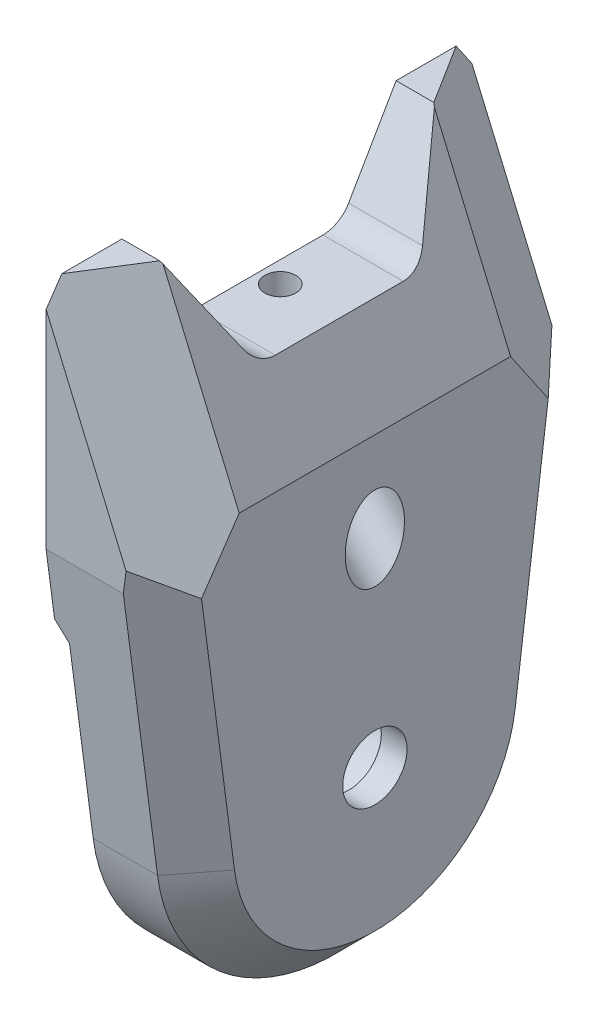
SolidWorks part; units mm, degrees
note: The reader was unsure of these and kept them because the rebuilt part matched: shared geometry of "Sketch1<7>", "Sketch1<4>", "Sketch1<6>", "Sketch2<3>".
ref_plane "Front" through (0, 0, 0) normal (0, 0, 1) x (1, 0, 0)
ref_plane "Top" through (0, 0, 0) normal (0, 1, 0) x (1, 0, 0)
ref_plane "Right" through (0, 0, 0) normal (1, 0, 0) x (0, 0, -1)
sketch "Sketch1" plane through (0, 0, 0) normal (1, 0, 0) x (0, 0, -1)
  line L0 (-5.9491, -0.7796) -> (-7.27, 9.3) construction
  line L1 (-7.27, 9.3) -> (-7.27, 11.925) construction
  line L2 (-7.27, 11.925) -> (7.27, 11.925) construction
  line L3 (7.27, 11.925) -> (7.27, 9.3) construction
  line L4 (7.27, 9.3) -> (5.9491, -0.7796) construction
  line L5 (0, 0) -> (0, 11.925) construction
  line L7 (8.27, 18.195) -> (8.27, 9.2348)
  line L8 (8.27, 9.2348) -> (6.9407, -0.9095)
  line L9 (-6.9407, -0.9095) -> (-8.27, 9.2348)
  line L10 (-8.27, 9.2348) -> (-8.27, 18.195)
  line L12 (-7.8382, 5.94) -> (7.8382, 5.94) construction
  line L14 (-8.27, 9.2348) -> (-8.27, 11.925) construction
  line L15 (-8.27, 18.195) -> (-2.325, 18.195)
  line L16 (-2.325, 18.195) -> (-2.325, 14.425)
  line L17 (8.27, 11.925) -> (8.27, 9.2348) construction
  line L18 (8.27, 18.195) -> (2.325, 18.195)
  line L19 (2.325, 18.195) -> (2.325, 14.425)
  line L20 (-2.325, 14.425) -> (2.325, 14.425)
  line L21 (-4.5789, 5.94) -> (-5.5981, 6.5285) construction
  line L22 (4.5789, 5.94) -> (5.5981, 6.5285) construction
  line L23 (-5.5981, 6.5285) -> (-8.105, 7.9758) construction
  line L24 (5.5981, 6.5285) -> (8.105, 7.9758) construction
  line L25 (5.3584, 4.658) -> (7.8595, 6.102)
  line L26 (-5.3584, 4.658) -> (-7.8595, 6.102)
  line L27 (-5.3584, 4.658) -> (-8.855, 6.6768) construction
  line L28 (5.3584, 4.658) -> (8.855, 6.6768) construction
  arc A0 (-5.9491, -0.7796) -> (5.9491, -0.7796) centre (0, 0) ccw construction
  circle A1 centre (0, 0) radius 2.25
  circle A2 centre (0, 0) radius 1.25
  arc A3 (-6.9407, -0.9095) -> (6.9407, -0.9095) centre (0, 0) ccw
  circle A4 centre (-6.25, 11.925) radius 1.05
  circle A5 centre (6.25, 11.925) radius 1.05
  arc A6 (-5.5981, 6.5285) -> (5.5981, 6.5285) centre (0, 0) cw construction
  arc A7 (-4.5789, 5.94) -> (4.5789, 5.94) centre (0, 0) cw construction
  arc A8 (-5.3584, 4.658) -> (5.3584, 4.658) centre (0, 0) cw
  dimension "D4" = 6
  dimension "D5" = 7
  dimension "D7" = 4.5
  dimension "D8" = 2.5
  dimension "D12" = 2.1
  dimension "D9" = 7.5
  dimension "D15" = 8.6
  dimension "D1" = 14.54
  dimension "D2" = 11.925
  dimension "D3" = 2.625
  dimension "D6" = 5.985
  dimension "D10" = 4.65
  dimension "D11" = 3.77
  dimension "D13" = 6.25
  dimension "D14" = 2.5
  dimension "D16" = 120
  dimension "D17" = 1.5
extrude "Boss-Extrude4" add sketch "Sketch1<7>" against normal blind 4.5 contours L23 A6 L24 L8 L7 L18 L19 L20 L16 L15 L10 L9 A4 A5 | A4 | A5
sketch "Sketch1<7>" plane through (0, 0, 0) normal (1, 0, 0) x (0, 0, -1) same geometry as "Sketch1"
extrude "Boss-Extrude1" add sketch "Sketch1" against normal blind 4
extrude "Boss-Extrude2" add sketch "Sketch1<4>" against normal blind 1 contours A1 A2
sketch "Sketch1<4>" plane through (0, 0, 0) normal (1, 0, 0) x (0, 0, -1) same geometry as "Sketch1"
chamfer "Chamfer1" distance 3 angle 60 2 edges at (-2.25, 18.195, -2.325) (-2.25, 18.195, 2.325)
fillet "Fillet1" radius 1.15 2 edges at (-2.25, 14.425, -3.1484) (-2.25, 14.425, 3.1484)
chamfer "Chamfer2" distance 7 distance2 3 1 edges at (0, 18.195, 6.7975)
chamfer "Chamfer3" distance 3 angle 30 2 edges at (-1.5, 14.695, -8.27) (-1.5, 14.695, 8.27)
chamfer "Chamfer4" distance 1.5 angle 45 3 edges at (0, 3.1406, 7.4714) (0, 3.1406, -7.4714) (0, -7, 0)
extrude "Cut-Extrude1" cut sketch "Sketch1<6>" against normal through all from offset 2 contours A5 | A4 offset against normal yes
sketch "Sketch1<6>" plane through (0, 0, 0) normal (1, 0, 0) x (0, 0, -1) same geometry as "Sketch1"
sketch "Sketch2" plane through (0, 0, 0) normal (0, 0, 1) x (1, 0, 0)
  line L0 (-2.9428, 10.6572) -> (4.1283, 3.5862)
  line L1 (-4.5, 14.425) -> (-1.3843, 14.425)
  line L2 (-4.5, 14.425) -> (-1.3843, 14.425) construction
  line L3 (-3.675, 14.425) -> (-3.675, 12.425)
  arc A0 (-3.675, 12.425) -> (-2.9428, 10.6572) centre (-1.175, 12.425) ccw
  point P7 (-3.675, 14.425)
  dimension "D4" = 2.5
  dimension "D1" = 2
  dimension "D2" = 45
  dimension "D3" = 3.675
  dimension "D5" = 10
sweep "Cut-Sweep1" cut path "Sketch2" circular profile diameter 1.2 parameters "D3"=1.2
sweep "Cut-Sweep2" cut path "Sketch2<3>" circular profile diameter 2.3 parameters "D3"=2.3
sketch "Sketch2<3>" plane through (0, 0, 0) normal (0, 0, 1) x (1, 0, 0) same geometry as "Sketch2"
chamfer "Chamfer5" distance 0.5 angle 45 3 edges at (-4.5, 5.38, -6.609) (-4.5, 7.1, 0) (-4.5, 5.38, 6.609)
